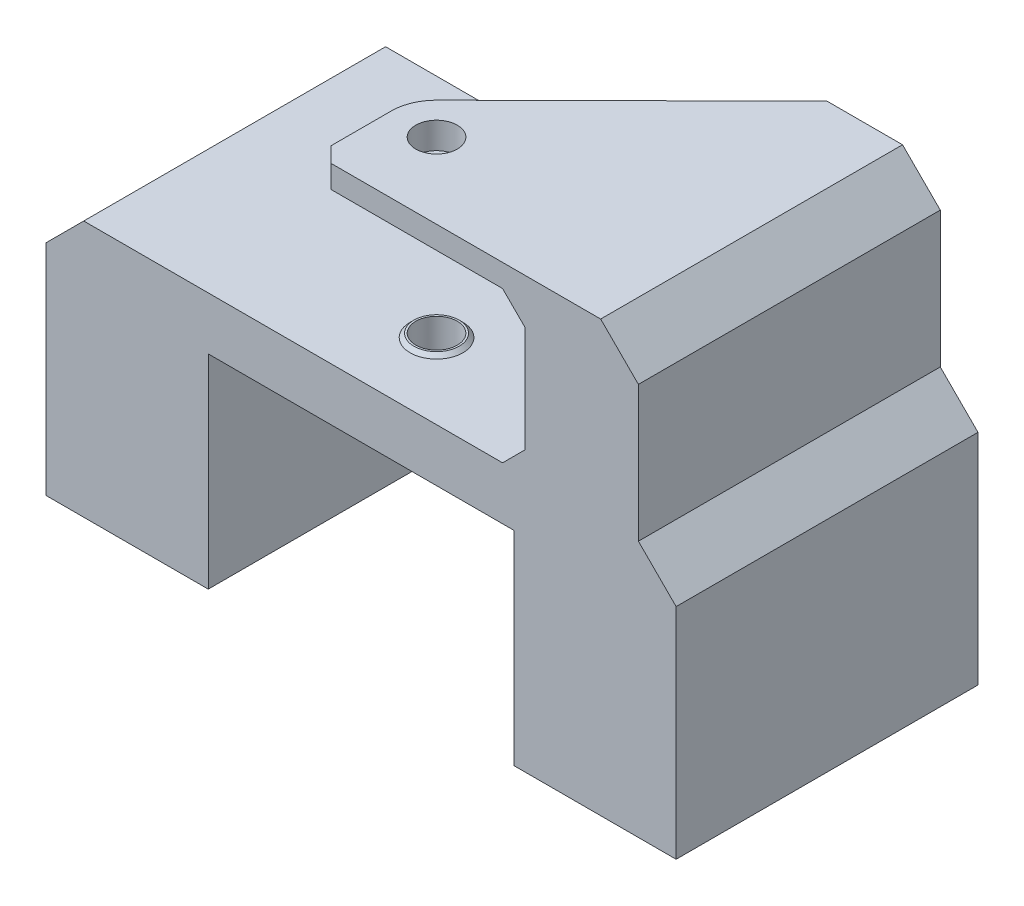
SolidWorks part; units mm, degrees
ref_plane "Front Plane" through (0, 0, 0) normal (0, 0, 1) x (1, 0, 0)
ref_plane "Top Plane" through (0, 0, 0) normal (0, 1, 0) x (1, 0, 0)
ref_plane "Right Plane" through (0, 0, 0) normal (1, 0, 0) x (0, 0, -1)
sketch "Sketch1" plane through (0, 0, 0) normal (0, 0, 1) x (1, 0, 0)
  line L0 (-20.25, 0) -> (20.25, 0)
  line L1 (20.25, 0) -> (20.25, -27)
  line L2 (20.25, -27) -> (41.75, -27)
  line L3 (41.75, -27) -> (41.75, 7)
  line L4 (41.75, 7) -> (-41.75, 7)
  line L5 (0, 0) -> (0, -13.5) construction
  line L6 (-41.75, -27) -> (-41.75, 7)
  line L7 (-20.25, -27) -> (-41.75, -27)
  line L8 (-20.25, 0) -> (-20.25, -27)
  circle A0 centre (31.75, -10) radius 4.05
  circle A1 centre (-31.75, -10) radius 4.05
  point P12 (0, 7)
  dimension "D5" = 8.1
  dimension "D1" = 7
  dimension "D2" = 20.25
  dimension "D3" = 27
  dimension "D4" = 21.5
  dimension "D6" = 31.75
  dimension "D7" = 10
extrude "Boss-Extrude1" add sketch "Sketch1" along normal blind 40
sketch "Sketch2" plane through (0, 0, 0) normal (0, -1, 0) x (-1, 0, 0)
  line L0 (0, -40) -> (0, -30) construction
  line L1 (20.25, -40) -> (-20.25, -40) construction
  circle A0 centre (0, -30) radius 2.75
  dimension "D1" = 5.5
  dimension "D2" = 10
extrude "Cut-Extrude1" cut sketch "Sketch2" against normal blind 40
chamfer "Chamfer1" distance 5 angle 45 1 edges at (41.75, 7, 20)
ref_plane "Plane1" through (0, 27, 0) normal (0, 1, 0) x (1, 0, 0)
sketch "Sketch4" plane through (0, 7, 0) normal (0, 1, 0) x (1, 0, 0)
  line L0 (36.75, -40) -> (-41.75, -40) construction
  line L5 (36.75, 0) -> (21.75, 0)
  line L6 (36.75, 0) -> (36.75, -40)
  line L7 (36.75, -40) -> (21.75, -40)
  line L8 (21.75, 0) -> (21.75, -40)
  dimension "D3" = 15
extrude "Boss-Extrude2" add sketch "Sketch4" along normal blind 20
sketch "Sketch5" plane through (0, 27, 0) normal (0, 1, 0) x (1, 0, 0)
  line L0 (21.75, -40) -> (-6, -40)
  line L3 (21.75, 0) -> (-4.2233, -25.7381)
  line L4 (-6, -30) -> (-6, -40)
  line L5 (20.5796, -40) -> (36.75, -40)
  line L6 (36.75, -40) -> (36.75, 0)
  line L7 (36.75, 0) -> (21.75, 0)
  arc A0 (-4.2233, -25.7381) -> (-6, -30) centre (0, -30) ccw
  circle A1 centre (0, -30) radius 2.75
  dimension "D1" = 12
  dimension "D2" = 5.5
extrude "Boss-Extrude3" add sketch "Sketch5" along normal blind 3 contours A1 region at (19.2158, 27, 22.9833)
chamfer "Chamfer2" distance 5 angle 45 1 edges at (36.75, 30, 20)
chamfer "Chamfer3" distance 5 angle 45 1 edges at (-41.75, 7, 20)
sketch "Sketch6" plane through (0, 0, 40) normal (0, 0, 1) x (1, 0, 0)
  circle A0 centre (-31.75, -10) radius 4.05
  circle A1 centre (31.75, -10) radius 4.05
extrude "Boss-Extrude4" add sketch "Sketch6" against normal blind 5
sketch "Sketch7" plane through (0, -27, 0) normal (0, -1, 0) x (-1, 0, 0)
  line L0 (-31, 0) -> (-31, -40) construction
  line L1 (-20.25, 0) -> (-41.75, 0) construction
  line L2 (-20.25, -40) -> (-41.75, -40) construction
  circle A0 centre (-31, -5) radius 1.95
  circle A1 centre (-31, -25) radius 1.95
  dimension "D1" = 3.9
  dimension "D2" = 5
  dimension "D3" = 20
extrude "Cut-Extrude2" cut sketch "Sketch7" against normal blind 20
mirror "Mirror1" about plane through (0, 0, 0) normal (1, 0, 0) of "Cut-Extrude2"
chamfer "Chamfer4" distance 2 angle 45 1 edges at (-6, 28.5, 40)
chamfer "Chamfer5" distance 3 angle 45 2 edges at (21.75, 7, 20) (21.75, 27, 20)
sketch "Sketch8" plane through (0, 7, 0) normal (0, 1, 0) x (1, 0, 0)
  circle A0 centre (0, -30) radius 2.75
  circle A1 centre (0, -30) radius 3
  dimension "D1" = 6
extrude "Boss-Extrude5" add sketch "Sketch8" along normal blind 0.5
chamfer "Chamfer6" distance 0.5 angle 45 1 edges at (0, 7, 27)
sketch "Sketch9" plane through (0, 27, 0) normal (0, -1, 0) x (-1, 0, 0)
  circle A0 centre (0, -30) radius 2.75
  circle A1 centre (0, -30) radius 3
  dimension "D1" = 6
extrude "Boss-Extrude6" add sketch "Sketch9" along normal blind 0.5
chamfer "Chamfer7" distance 0.5 angle 45 1 edges at (0, 27, 33)
